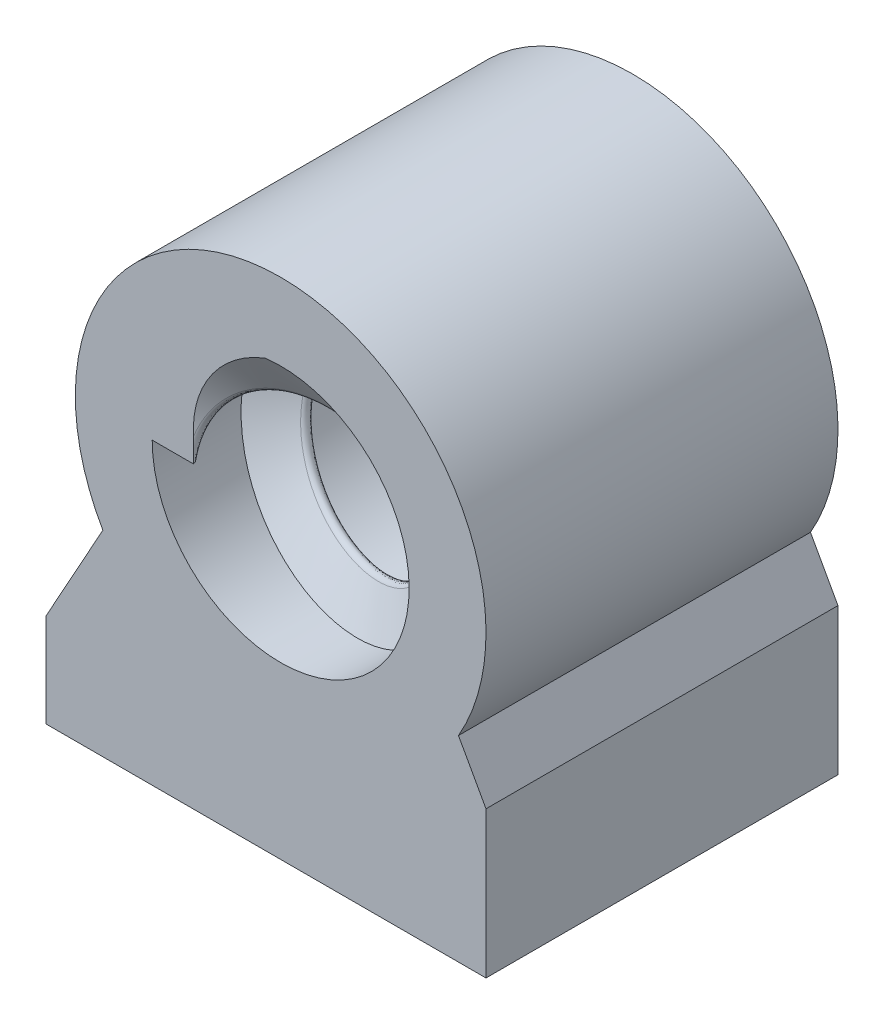
SolidWorks part; units mm, degrees
ref_plane "Front Plane" through (0, 0, 0) normal (0, 0, 1) x (1, 0, 0)
ref_plane "Top Plane" through (0, 0, 0) normal (0, 1, 0) x (1, 0, 0)
ref_plane "Right Plane" through (0, 0, 0) normal (1, 0, 0) x (0, 0, -1)
sketch "Sketch1" plane through (0, 0, 0) normal (0, 0, 1) x (1, 0, 0)
  circle A0 centre (0, 0) radius 17.5
  dimension "D1" = 35
extrude "Boss-Extrude1" add sketch "Sketch1" along normal blind 30
sketch "Sketch5" plane through (0, 0, 0) normal (0, 0, -1) x (-1, 0, 0)
  circle A0 centre (0, 0) radius 10.95
  dimension "D1" = 21.9
extrude "Cut-Extrude2" cut sketch "Sketch5" against normal through all
ref_plane "Plane1" through (0, 0, -10) normal (0, 0, -1) x (-1, 0, 0)
sketch "Sketch6" plane through (0, 0, -10) normal (0, 0, -1) x (-1, 0, 0)
  circle A0 centre (0, 0) radius 10.95 construction
  circle A1 centre (0, 0) radius 10.95
curve "Helix/Spiral2" pitch 10 height 40 turns 4
sketch "Sketch7" plane through (0, 0, 0) normal (1, 0, 0) x (0, 0, -1)
  line L0 (7.5, -6.95) -> (7.5, -10.95) construction
  line L1 (7.067, -7.7) -> (5.1906, -10.95)
  line L2 (5.1906, -10.95) -> (9.8094, -10.95)
  line L3 (7.933, -7.7) -> (9.8094, -10.95)
  arc A0 (7.933, -7.7) -> (7.067, -7.7) centre (7.5, -7.95) ccw
  dimension "D3" = 0.5
  dimension "D1" = 60
  dimension "D2" = 4
sweep "Sweep2" add profiles "Sketch7" path "Helix/Spiral2"
sketch "Sketch8" plane through (0, 0, 0) normal (0, 0, -1) x (-1, 0, 0)
  circle A0 centre (0, 0) radius 17.5
  circle A1 centre (0, 0) radius 17.5 construction
extrude "Cut-Extrude3" cut sketch "Sketch8" along normal through all
sketch "Sketch9" plane through (0, 0, 30) normal (0, 0, 1) x (1, 0, 0)
  circle A0 centre (0, 0) radius 17.5
  circle A1 centre (0, 0) radius 17.5 construction
extrude "Cut-Extrude4" cut sketch "Sketch9" along normal through all
sketch "Sketch10" plane through (0, 0, 0) normal (0, 0, -1) x (-1, 0, 0)
  line L0 (-20, -17.5) -> (0, 0) construction
  line L1 (-20, -17.5) -> (20, -17.5)
  line L2 (-20, -17.5) -> (-20, -37.4773)
  line L3 (-20, -37.4773) -> (20, -37.4773)
  line L4 (20, -17.5) -> (20, -37.4773)
  line L5 (0, 0) -> (20, -17.5) construction
  circle A0 centre (0, 0) radius 17.5 construction
  dimension "D1" = 40
  dimension "D2" = 19.9773
extrude "Boss-Extrude2" add sketch "Sketch10" against normal blind 40 separate body
sketch "Sketch11" plane through (0, 0, 0) normal (0, 0, -1) x (-1, 0, 0)
  line L1 (-20, -17.5) -> (20, -17.5)
  line L2 (-20, -17.5) -> (-20, -37.4773)
  line L3 (-20, -37.4773) -> (20, -37.4773)
  line L4 (20, -17.5) -> (20, -37.4773)
extrude "Boss-Extrude3" add sketch "Sketch11" along normal blind 10
sketch "Sketch13" plane through (0, 0, 0) normal (0, 0, -1) x (-1, 0, 0)
  line L0 (0, -17.5) -> (-20, -17.5)
  line L1 (20, -17.5) -> (-20, -17.5) construction
  line L2 (-20, -17.5) -> (-15.1539, -8.7527)
  circle A0 centre (0, 0) radius 17.5 construction
  arc A1 (-15.1539, -8.7527) -> (0, -17.5) centre (0, 0) ccw
  dimension "D1" = 10
extrude "Boss-Extrude4" add sketch "Sketch13" against normal up to surface (30 mm away) up to face at (-3.7285, 0.054, 30)
ref_plane "Plane2" through (0, 0, 0) normal (1, 0, 0) x (0, 0, -1)
mirror "Mirror1" about plane through (0, 0, 0) normal (1, 0, 0) of "Boss-Extrude4"
sketch "Sketch14" plane through (0, -37.4773, 0) normal (0, -1, 0) x (1, 0, 0)
  line L0 (-20, 40) -> (20, -10) construction
  line L2 (-20, -10) -> (20, 40) construction
  line L3 (10, -4.2426) -> (-10, -4.2426) construction
  line L4 (10, -4.2426) -> (10, 34.2426) construction
  line L5 (10, 34.2426) -> (-10, 34.2426) construction
  line L6 (-10, -4.2426) -> (-10, 34.2426) construction
  line L7 (10, -4.2426) -> (-10, 34.2426) construction
  line L8 (10, 34.2426) -> (-10, -4.2426) construction
  circle A0 centre (-10, 34.2426) radius 1.905
  circle A1 centre (10, 34.2426) radius 1.905
  circle A2 centre (-10, -4.2426) radius 1.905
  circle A3 centre (10, -4.2426) radius 1.905
  point P8 (0, 15)
  dimension "D3" = 3.81
  dimension "D1" = 38.4853
  dimension "D2" = 20
extrude "Cut-Extrude5" cut sketch "Sketch14" against normal through all
ref_plane "Plane3" through (0, -20.6734, 0) normal (0, 1, 0) x (1, 0, 0)
sketch "Sketch15" plane through (0, -20.6734, 0) normal (0, 1, 0) x (1, 0, 0)
  circle A0 centre (-10, 4.2426) radius 3.9243
  circle A1 centre (10, 4.2426) radius 3.9243
  circle A2 centre (10, -34.2426) radius 3.9243
  circle A3 centre (-10, -34.2426) radius 3.9243
  dimension "D1" = 7.8486
extrude "Cut-Extrude7" cut sketch "Sketch15" along normal through all
sketch "Sketch16" plane through (-20, 0, 0) normal (-1, 0, 0) x (0, 0, 1)
  line L0 (40, -37.4773) -> (40, -17.5) construction
  line L1 (-10, -17.5) -> (40, -17.5)
  line L2 (-10, -17.5) -> (-10, -37.4773)
  line L3 (-10, -37.4773) -> (40, -37.4773)
  line L4 (40, -17.5) -> (40, -37.4773)
  line L5 (40, -37.4773) -> (-10, -37.4773) construction
extrude "Boss-Extrude5" add sketch "Sketch16" along normal blind 22
ref_plane "Plane4" through (-37, 0, 0) normal (-1, 0, 0) x (0, 0, 1)
sketch "Sketch17" plane through (-37, 0, 0) normal (-1, 0, 0) x (0, 0, 1)
  line L0 (40, -17.5) -> (-10, -17.5) construction
  line L5 (4, -24.5) -> (-10, -17.5) construction
  line L6 (40, -17.5) -> (26, -24.5) construction
  line L12 (4, -24.5) -> (8.5, -24.5)
  line L13 (11, -24.5) -> (26, -24.5)
  line L14 (26, -17.5) -> (4, -17.5)
  line L15 (4, -17.5) -> (4, -24.5)
  line L16 (26, -17.5) -> (26, -24.5)
  line L17 (8.5, -24.5) -> (8.5, -29.4889)
  line L18 (11, -24.5) -> (11, -29.4889)
  line L19 (8.5, -29.4889) -> (11, -29.4889)
  dimension "D1" = 22
  dimension "D2" = 7
  dimension "D3" = 2.5
  dimension "D4" = 4.5
extrude "Cut-Extrude8" cut sketch "Sketch17" against normal blind 12
sketch "Sketch19" plane through (0, -17.5, 0) normal (0, 1, 0) x (1, 0, 0)
  line L0 (-42, -40) -> (-42, 10) construction
  line L1 (-42, -12) -> (-49, -12)
  line L2 (-42, -12) -> (-42, -18)
  line L3 (-42, -18) -> (-49, -18)
  line L5 (-54, -12) -> (-37, -4) construction
  line L6 (-54, -18) -> (-37, -26) construction
  line L7 (-49, -7) -> (-37, -4) construction
  line L8 (-54, -7) -> (-49, -7)
  line L10 (-54, -23) -> (-49, -23)
  line L11 (-49, -7) -> (-49, -12)
  line L12 (-49, -23) -> (-37, -26) construction
  line L13 (-49, -18) -> (-49, -23)
  line L14 (-54, -7) -> (-54, -23)
  dimension "D1" = 6
  dimension "D2" = 16
  dimension "D3" = 7
  dimension "D4" = 12
extrude "Boss-Extrude6" add sketch "Sketch19" against normal through all
sketch "Sketch20" plane through (0, -17.5, 0) normal (0, 1, 0) x (1, 0, 0)
  line L0 (-42, -12) -> (-42, 10) construction
  line L1 (-54, -7) -> (-49, -7)
  line L2 (-54, -7) -> (-54, -23)
  line L3 (-54, -23) -> (-49, -23)
  line L4 (-49, -7) -> (-49, -12)
  line L5 (-42, -12) -> (-49, -12)
  line L7 (-42, -18) -> (-49, -18)
  line L9 (-42, -7) -> (-37, -7)
  line L10 (-42, -7) -> (-42, -12)
  line L11 (-42, -23) -> (-37, -23)
  line L12 (-37, -7) -> (-37, -23)
  line L13 (-37, -26) -> (-37, -4) construction
  line L14 (-42, -18) -> (-42, -23)
  line L15 (-49, -18) -> (-49, -23)
extrude "Boss-Extrude7" add sketch "Sketch20" along normal blind 22
fillet "Fillet1" radius 2 4 edges at (-42, -16.4886, 12) (-42, -16.4886, 18) (-49, -16.4886, 18) (-49, -16.4886, 12)
sketch "Sketch21" plane through (0, -37.4773, 0) normal (0, -1, 0) x (1, 0, 0)
  line L0 (-42, -10) -> (-42, 10) construction
  line L1 (-49, 23) -> (-42, 23)
  line L2 (-49, 23) -> (-49, 7)
  line L3 (-49, 7) -> (-42, 7)
  line L4 (-42, 23) -> (-42, 7)
  line L5 (-49, 7) -> (-54, 7) construction
extrude "Boss-Extrude8" add sketch "Sketch21" against normal blind 2
sketch "Sketch22" plane through (0, -17.5, 0) normal (0, 1, 0) x (1, 0, 0)
  line L1 (-42, 10) -> (20, 10)
  line L3 (-42, -40) -> (20, -40)
  line L4 (20, 10) -> (20, -40)
  line L5 (-20, 0) -> (17.5, 0)
  line L6 (-20, 0) -> (-20, -30)
  line L7 (-20, -30) -> (17.5, -30)
  line L8 (17.5, 0) -> (17.5, -30)
  line L9 (-42, 10) -> (-59.6043, 10)
  line L10 (-42, -40) -> (-42, -43.5332)
  line L11 (-42, -43.5332) -> (-59.6043, -43.5332)
  line L12 (-59.6043, 10) -> (-59.6043, -43.5332)
extrude "Cut-Extrude9" cut sketch "Sketch22" against normal through all and the other way through all
sketch "Sketch23" plane through (0, -37.4773, 0) normal (0, -1, 0) x (1, 0, 0)
  line L0 (17.5, 30) -> (17.5, 0) construction
  line L1 (-20, 30) -> (17.5, 30)
  line L2 (-20, 30) -> (-20, 0)
  line L3 (-20, 0) -> (17.5, 0)
  line L4 (17.5, 30) -> (17.5, 0)
extrude "Cut-Extrude10" cut sketch "Sketch23" against normal blind 12
